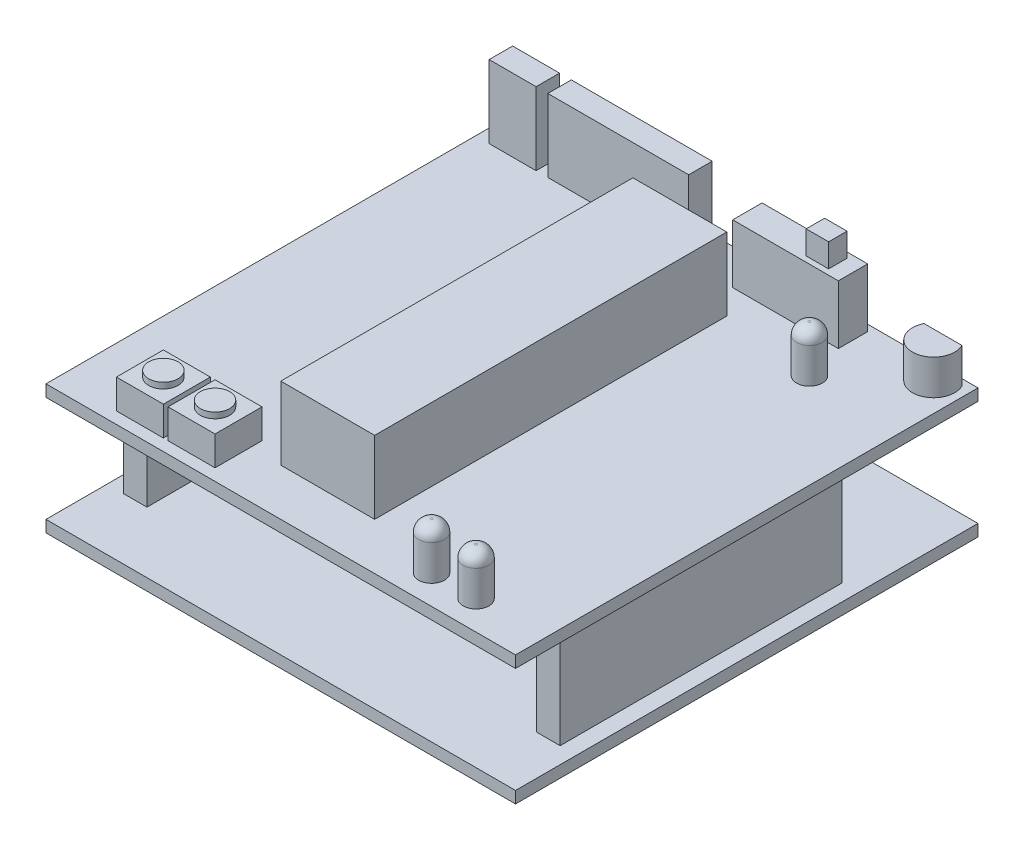
SolidWorks part; units mm, degrees
ref_plane "Front Plane" through (0, 0, 0) normal (0, 0, 1) x (1, 0, 0)
ref_plane "Top Plane" through (0, 0, 0) normal (0, 1, 0) x (1, 0, 0)
ref_plane "Right Plane" through (0, 0, 0) normal (1, 0, 0) x (0, 0, -1)
sketch "Sketch1" plane through (0, 0, 0) normal (0, 1, 0) x (1, 0, 0)
  line L1 (-25.4, -25.019) -> (25.4, -25.019)
  line L2 (-25.4, -25.019) -> (-25.4, 25.019)
  line L3 (-25.4, 25.019) -> (25.4, 25.019)
  line L4 (25.4, -25.019) -> (25.4, 25.019)
  line L5 (-25.4, -25.019) -> (25.4, 25.019) construction
  line L6 (-25.4, 25.019) -> (25.4, -25.019) construction
  point P0 (0, 0)
  dimension "D1" = 50.8
  dimension "D2" = 50.038
extrude "Boss-Extrude1" add sketch "Sketch1" along normal blind 1.27
sketch "Sketch2" plane through (0, 1.27, 0) normal (0, 1, 0) x (1, 0, 0)
  line L0 (-25.4, -25.019) -> (25.4, -25.019) construction
  line L1 (-23.622, -18.415) -> (-21.082, -18.415)
  line L2 (-23.622, -18.415) -> (-23.622, 12.065)
  line L3 (-23.622, 12.065) -> (-21.082, 12.065)
  line L4 (-21.082, -18.415) -> (-21.082, 12.065)
  line L5 (-25.4, 25.019) -> (-25.4, -25.019) construction
  line L6 (0, -0.6985) -> (0, 0.6985) construction
  line L7 (23.622, 12.065) -> (21.082, 12.065)
  line L8 (21.082, -18.415) -> (21.082, 12.065)
  line L9 (23.622, -18.415) -> (21.082, -18.415)
  line L10 (23.622, -18.415) -> (23.622, 12.065)
  dimension "D1" = 2.54
  dimension "D2" = 30.48
  dimension "D3" = 6.604
  dimension "D4" = 1.778
extrude "Boss-Extrude2" add sketch "Sketch2" along normal blind 11.43
sketch "Sketch3" plane through (0, 1.27, 0) normal (0, 1, 0) x (1, 0, 0)
  line L0 (25.4, 25.019) -> (-25.4, 25.019) construction
  line L1 (-5.08, 23.495) -> (5.08, 23.495)
  line L2 (-5.08, 23.495) -> (-5.08, 3.175)
  line L3 (-5.08, 3.175) -> (5.08, 3.175)
  line L4 (5.08, 23.495) -> (5.08, 3.175)
  point P4 (0, 3.175)
  dimension "D1" = 20.32
  dimension "D2" = 10.16
  dimension "D3" = 1.524
extrude "Boss-Extrude3" add sketch "Sketch3" along normal blind 3.81
sketch "Sketch4" plane through (0, 12.7, 0) normal (0, 1, 0) x (1, 0, 0)
  line L4 (25.4, -25.019) -> (25.4, 25.019)
  line L5 (25.4, 25.019) -> (-25.4, 25.019)
  line L6 (-25.4, 25.019) -> (-25.4, -25.019)
  line L7 (-25.4, -25.019) -> (25.4, -25.019)
  line L8 (25.4, -25.019) -> (25.4, 25.019)
  line L9 (25.4, 25.019) -> (-25.4, 25.019)
  line L10 (-25.4, 25.019) -> (-25.4, -25.019)
  line L11 (-25.4, -25.019) -> (25.4, -25.019)
  dimension "D1" = 0
extrude "Boss-Extrude4" add sketch "Sketch4" along normal blind 1.27
sketch "Sketch5" plane through (0, 13.97, 0) normal (0, 1, 0) x (1, 0, 0)
  line L0 (-25.4, -25.019) -> (25.4, -25.019) construction
  line L1 (-5.08, -19.939) -> (5.08, -19.939)
  line L2 (-5.08, -19.939) -> (-5.08, 18.161)
  line L3 (-5.08, 18.161) -> (5.08, 18.161)
  line L4 (5.08, -19.939) -> (5.08, 18.161)
  line L5 (-25.4, 25.019) -> (-25.4, -25.019) construction
  line L6 (-23.9364, 24.003) -> (-18.8564, 24.003)
  line L7 (-23.9364, 24.003) -> (-23.9364, 21.463)
  line L8 (-23.9364, 21.463) -> (-18.8564, 21.463)
  line L9 (-18.8564, 24.003) -> (-18.8564, 21.463)
  line L10 (-17.5864, 24.003) -> (-2.3464, 24.003)
  line L11 (-17.5864, 24.003) -> (-17.5864, 21.463)
  line L12 (-17.5864, 21.463) -> (-2.3464, 21.463)
  line L13 (-2.3464, 24.003) -> (-2.3464, 21.463)
  line L14 (2.7336, 24.3205) -> (14.1636, 24.3205)
  line L15 (2.7336, 24.3205) -> (2.7336, 21.1455)
  line L16 (2.7336, 21.1455) -> (14.1636, 21.1455)
  line L17 (14.1636, 24.3205) -> (14.1636, 21.1455)
  line L18 (-13.462, -23.749) -> (-8.382, -23.749)
  line L19 (-13.462, -23.749) -> (-13.462, -18.669)
  line L20 (-13.462, -18.669) -> (-8.382, -18.669)
  line L21 (-8.382, -23.749) -> (-8.382, -18.669)
  line L22 (-13.97, -23.749) -> (-19.05, -23.749)
  line L23 (-13.97, -23.749) -> (-13.97, -18.669)
  line L24 (-13.97, -18.669) -> (-19.05, -18.669)
  line L25 (-19.05, -23.749) -> (-19.05, -18.669)
  line L26 (20.2609, 24.3205) -> (24.3565, 24.3205)
  line L27 (25.4, 25.019) -> (-25.4, 25.019) construction
  circle A0 centre (13.1668, -21.867) radius 1.397
  circle A1 centre (17.9781, -21.867) radius 1.397
  circle A2 centre (15.1351, 17.0468) radius 1.397
  arc A3 (20.2609, 24.3205) -> (24.3565, 24.3205) centre (22.3087, 23.3045) ccw
  point P4 (0, 18.161)
  point P20 (2.7336, 22.733)
  point P21 (-2.3464, 22.733)
  point P40 (22.3087, 22.9545)
  dimension "D15" = 2.794
  dimension "D16" = 2.286
  dimension "D1" = 10.16
  dimension "D2" = 38.1
  dimension "D3" = 5.08
  dimension "D4" = 2.54
  dimension "D5" = 5.08
  dimension "D6" = 1.27
  dimension "D7" = 15.24
  dimension "D8" = 11.43
  dimension "D9" = 3.175
  dimension "D10" = 5.08
  dimension "D11" = 5.08
  dimension "D12" = 0.508
  dimension "D13" = 6.35
  dimension "D14" = 1.27
  dimension "D17" = 1.016
  dimension "D18" = 1.016
extrude "Boss-Extrude5" add sketch "Sketch5" along normal blind 7.874 contours L1 L4 L3 L2 | L10 L13 L12 L11 | L6 L9 L8 L7 region at (0, 13.97, 0.889)
extrude "Boss-Extrude6" add sketch "Sketch5<3>" along normal blind 3.175 contours L25 L22 L23 L24 | L18 L21 L20 L19 region at (-10.922, 13.97, 21.209) region at (-16.51, 13.97, 21.209)
sketch "Sketch5<3>" plane through (0, 13.97, 0) normal (0, 1, 0) x (1, 0, 0) same geometry as "Sketch5"
extrude "Boss-Extrude7" add sketch "Sketch5<4>" along normal blind 5.08 contours A0 | A1 | A2
sketch "Sketch5<4>" plane through (0, 13.97, 0) normal (0, 1, 0) x (1, 0, 0) same geometry as "Sketch5"
extrude "Boss-Extrude8" add sketch "Sketch5<5>" along normal blind 6.35 contours L14 L17 L16 L15
sketch "Sketch5<5>" plane through (0, 13.97, 0) normal (0, 1, 0) x (1, 0, 0) same geometry as "Sketch5"
extrude "Boss-Extrude9" add sketch "Sketch5<6>" along normal blind 3.81 contours A3 L26
sketch "Sketch5<6>" plane through (0, 13.97, 0) normal (0, 1, 0) x (1, 0, 0) same geometry as "Sketch5"
fillet "Fillet1" radius 1.27 3 edges at (17.9781, 19.05, 23.264) (13.1668, 19.05, 23.264) (15.1351, 19.05, -15.6498)
sketch "Sketch8" plane through (0, 17.145, 0) normal (0, 1, 0) x (1, 0, 0)
  line L0 (-19.05, -23.749) -> (-13.97, -18.669) construction
  line L1 (-13.97, -18.669) -> (-13.462, -18.669) construction
  line L2 (-13.462, -18.669) -> (-8.382, -23.749) construction
  circle A0 centre (-16.51, -21.209) radius 1.5875
  circle A1 centre (-10.922, -21.209) radius 1.5875
  dimension "D1" = 3.175
extrude "Boss-Extrude10" add sketch "Sketch8" along normal blind 0.635
sketch "Sketch9" plane through (0, 20.32, 0) normal (0, 1, 0) x (1, 0, 0)
  line L0 (8.4486, 21.1455) -> (14.1636, 24.3205) construction
  line L1 (2.7336, 21.1455) -> (14.1636, 21.1455) construction
  line L3 (10.0925, 21.7352) -> (12.5197, 21.7352)
  line L4 (10.0925, 21.7352) -> (10.0925, 23.7308)
  line L5 (10.0925, 23.7308) -> (12.5197, 23.7308)
  line L6 (12.5197, 21.7352) -> (12.5197, 23.7308)
  line L7 (10.0925, 21.7352) -> (12.5197, 23.7308) construction
  line L8 (10.0925, 23.7308) -> (12.5197, 21.7352) construction
  point P5 (11.3061, 22.733)
extrude "Boss-Extrude11" add sketch "Sketch9" along normal blind 2.54
